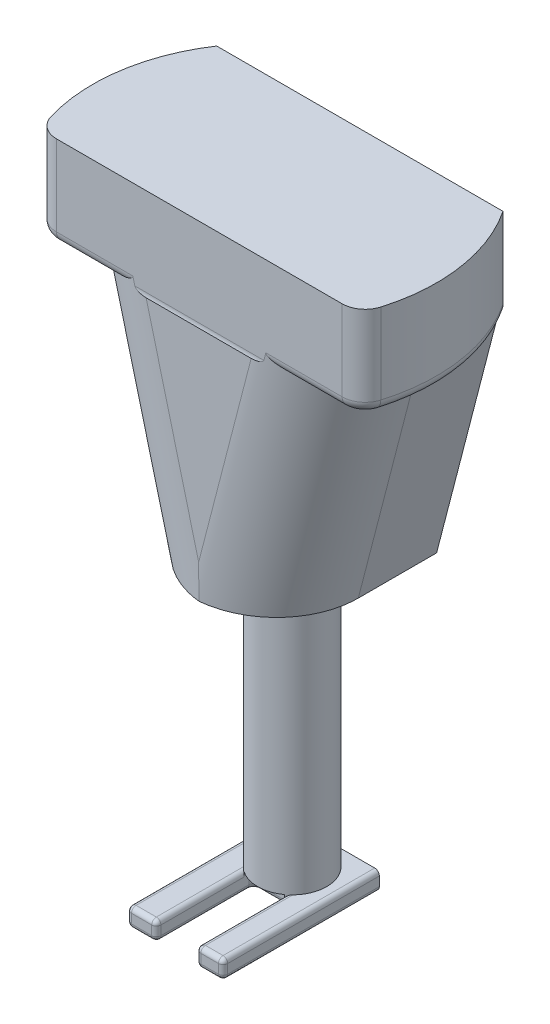
SolidWorks part; units mm, degrees
ref_plane "Front Plane" through (0, 0, 0) normal (0, 0, 1) x (1, 0, 0)
ref_plane "Top Plane" through (0, 0, 0) normal (0, 1, 0) x (1, 0, 0)
ref_plane "Right Plane" through (0, 0, 0) normal (1, 0, 0) x (0, 0, -1)
sketch "Sketch1" plane through (0, 0, 0) normal (0, 0, 1) x (1, 0, 0)
  line L0 (-30, 0) -> (30, 0)
  line L1 (16.6667, -51.4457) -> (-16.6667, -51.4457)
  line L2 (-30, 0) -> (-16.6667, -51.4457)
  line L3 (30, 0) -> (16.6667, -51.4457)
  point P4 (0, 0)
  point P8 (0, -51.4457)
  dimension "D1" = 60
  dimension "D2" = 33.3333
extrude "Boss-Extrude5" add sketch "Sketch1" along normal blind 35
fillet "Fillet9" radius 18 2 edges at (23.3333, -25.7228, 35) (-23.3333, -25.7228, 35)
sketch "Sketch16" plane through (0, 0, 0) normal (0, 1, 0) x (1, 0, 0)
  circle A0 centre (0, -20.6852) radius 37.3402
extrude "Boss-Extrude6" add sketch "Sketch16" along normal blind 20
sketch "Sketch17" plane through (0, 0, 0) normal (0, -1, 0) x (-1, 0, 0)
  line L1 (32.6586, 0) -> (-34.5797, 0)
  line L2 (32.6586, 0) -> (32.6586, 19.5421)
  line L3 (32.6586, 19.5421) -> (-34.5797, 19.5421)
  line L4 (-34.5797, 0) -> (-34.5797, 19.5421)
extrude "Cut-Extrude1" cut sketch "Sketch17" against normal blind 20
sketch "Sketch18" plane through (0, 0, 0) normal (0, -1, 0) x (1, 0, 0)
  line L1 (-38.2661, 34.852) -> (37.4378, 34.852)
  line L2 (-38.2661, 34.852) -> (-38.2661, 58.1264)
  line L3 (-38.2661, 58.1264) -> (37.4378, 58.1264)
  line L4 (37.4378, 34.852) -> (37.4378, 58.1264)
extrude "Cut-Extrude2" cut sketch "Sketch18" against normal blind 20
fillet "Fillet10" radius 5 1 edges at (-34.5484, 10, 34.852)
fillet "Fillet11" radius 5 1 edges at (34.5484, 10, 34.852)
fillet "Fillet15" radius 2.5 3 edges at (36.9217, 0, 15.1101) (34.0067, 0, 33.8574) (22.3992, 0, 34.852)
fillet "Fillet16" radius 2.5 3 edges at (-36.9217, 0, 15.1101) (-34.0067, 0, 33.8574) (-22.3992, 0, 34.852)
fillet "Fillet17" radius 2.5 1 edges at (0, 0, 34.852)
sketch "Sketch19" plane through (0, -51.4457, 0) normal (0, -1, 0) x (1, 0, 0)
  circle A0 centre (0, 14.6855) radius 7.5
extrude "Boss-Extrude8" add sketch "Sketch19" along normal blind 60
sketch "Sketch21" plane through (0, -111.4457, 0) normal (0, -1, 0) x (1, 0, 0)
  line L1 (10.2018, 5.9722) -> (-10.6875, 5.9722)
  line L2 (10.2018, 5.9722) -> (10.2018, 39.8971)
  line L3 (10.2018, 39.8971) -> (-10.6875, 39.8971)
  line L4 (-10.6875, 5.9722) -> (-10.6875, 39.8971)
  line L5 (10.2018, 5.9722) -> (-10.6875, 39.8971) construction
  line L6 (10.2018, 39.8971) -> (-10.6875, 5.9722) construction
  point P4 (-0.2429, 22.9347)
extrude "Boss-Extrude10" add sketch "Sketch21" along normal blind 4
sketch "Sketch22" plane through (0, -115.4457, 0) normal (0, -1, 0) x (1, 0, 0)
  line L1 (-4.2912, 41.688) -> (4.3722, 41.688)
  line L2 (-4.2912, 41.688) -> (-4.2912, 18.7745)
  line L3 (-4.2912, 18.7745) -> (4.3722, 18.7745)
  line L4 (4.3722, 41.688) -> (4.3722, 18.7745)
  line L5 (-4.2912, 41.688) -> (4.3722, 18.7745) construction
  line L6 (-4.2912, 18.7745) -> (4.3722, 41.688) construction
  point P4 (0.0405, 30.2313)
extrude "Cut-Extrude4" cut sketch "Sketch22" against normal blind 4
fillet "Fillet18" radius 1 1 edges at (-7.4894, -115.4457, 39.8971)
fillet "Fillet19" radius 1 1 edges at (7.287, -115.4457, 39.8971)
fillet "Fillet20" radius 1 3 edges at (-10.6875, -112.9457, 39.8971) (-10.6875, -115.1528, 39.6042) (-10.6875, -115.4457, 22.4347)
fillet "Fillet21" radius 1 3 edges at (10.2018, -112.9457, 39.8971) (10.2018, -115.1528, 39.6042) (10.2018, -115.4457, 22.4347)
fillet "Fillet22" radius 1 3 edges at (-6.9894, -111.4457, 39.8971) (-10.3947, -111.4457, 39.6042) (-10.6875, -111.4457, 22.4347)
fillet "Fillet23" radius 1 3 edges at (10.2018, -111.4457, 22.4347) (9.9089, -111.4457, 39.6042) (6.787, -111.4457, 39.8971)
fillet "Fillet24" radius 1 1 edges at (-4.2912, -113.4457, 18.7745)
fillet "Fillet25" radius 1 1 edges at (4.3722, -113.4457, 18.7745)
fillet "Fillet26" radius 1 13 edges at (4.3722, -111.4457, 29.8382) (4.3722, -111.7386, 39.6042) (-4.2912, -111.4457, 29.8669) (-4.2912, -111.7386, 39.6042) (-4.2912, -113.4457, 39.8971) (-4.2912, -115.1528, 39.6042) (-4.2912, -115.4457, 29.3358) (-3.9983, -115.4457, 19.0674) (0.0405, -115.4457, 18.7745) (4.0793, -115.4457, 19.0674) (4.3722, -115.4457, 29.3358) (4.3722, -115.1528, 39.6042) (4.3722, -113.4457, 39.8971)
